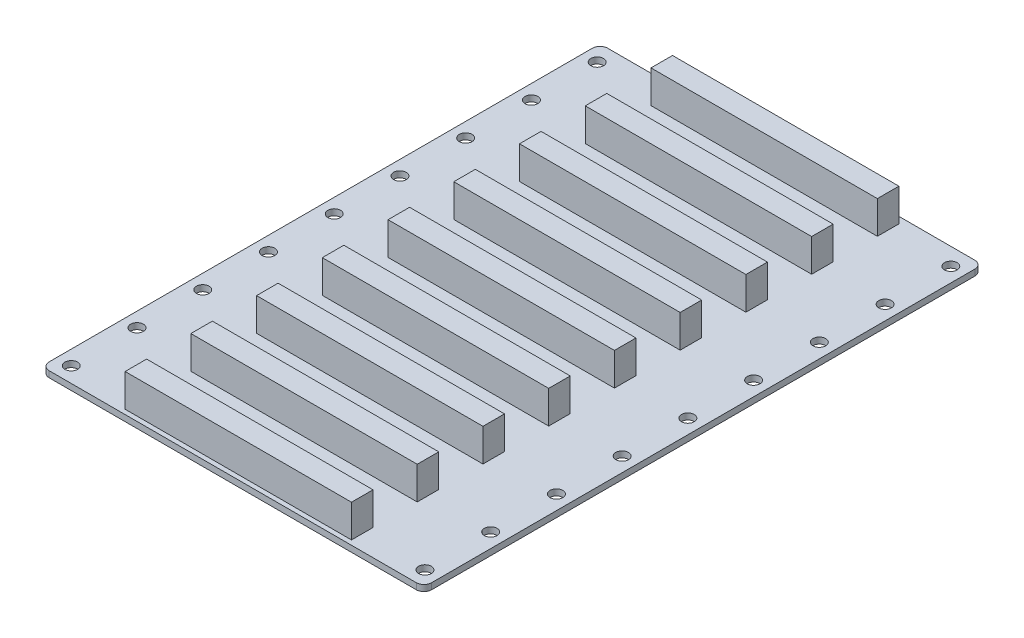
SolidWorks part; units mm, degrees
ref_plane "Front Plane" through (0, 0, 0) normal (0, 0, 1) x (1, 0, 0)
ref_plane "Top Plane" through (0, 0, 0) normal (0, 1, 0) x (1, 0, 0)
ref_plane "Right Plane" through (0, 0, 0) normal (1, 0, 0) x (0, 0, -1)
sketch "Sketch1" plane through (0, 0, 0) normal (0, 1, 0) x (1, 0, 0)
  line L1 (-49.75, -72.65) -> (49.75, -72.65)
  line L2 (-49.75, -72.65) -> (-49.75, 72.65)
  line L3 (-49.75, 72.65) -> (49.75, 72.65)
  line L4 (49.75, -72.65) -> (49.75, 72.65)
  line L5 (-49.75, -72.65) -> (49.75, 72.65) construction
  line L6 (-49.75, 72.65) -> (49.75, -72.65) construction
  point P0 (0, 0)
  dimension "D1" = 99.5
  dimension "D2" = 145.3
extrude "Boss-Extrude1" add sketch "Sketch1" along normal blind 1.6
sketch "Sketch3" plane through (0, 1.6, 0) normal (0, 1, 0) x (1, 0, 0)
  line L0 (0, 72.65) -> (0, -72.65) construction
  line L1 (49.75, 72.65) -> (-49.75, 72.65) construction
  line L2 (-49.75, -72.65) -> (49.75, -72.65) construction
  line L4 (-49.75, 72.65) -> (-49.75, -72.65) construction
  circle A1 centre (-46, -68.65) radius 1.65
  circle A3 centre (-46, -51.55) radius 1.65
  circle A4 centre (-46, -34.45) radius 1.65
  circle A5 centre (-46, -17.35) radius 1.65
  circle A6 centre (-46, -0.25) radius 1.65
  circle A7 centre (-46, 16.85) radius 1.65
  circle A8 centre (-46, 33.95) radius 1.65
  circle A9 centre (-46, 51.05) radius 1.65
  circle A10 centre (-46, 68.15) radius 1.65
  circle A11 centre (46, 68.15) radius 1.65
  circle A12 centre (46, 51.05) radius 1.65
  circle A13 centre (46, 33.95) radius 1.65
  circle A14 centre (46, 16.85) radius 1.65
  circle A15 centre (46, -0.25) radius 1.65
  circle A16 centre (46, -17.35) radius 1.65
  circle A17 centre (46, -34.45) radius 1.65
  circle A18 centre (46, -51.55) radius 1.65
  circle A19 centre (46, -68.65) radius 1.65
  dimension "D1" = 3.3
  dimension "D2" = 3.75
  dimension "D3" = 9
  dimension "D4" = 17.1
  dimension "D5" = 4
extrude "Cut-Extrude2" cut sketch "Sketch3" against normal up to surface (1.6 mm away) up to face at (0, 0, 0)
sketch "Sketch4" plane through (0, 1.6, 0) normal (0, 1, 0) x (1, 0, 0)
  line L0 (-29.195, -54.35) -> (-29.195, -48.75)
  line L1 (-29.195, -71.45) -> (29.695, -71.45)
  line L2 (-29.195, -71.45) -> (-29.195, -65.85)
  line L3 (-29.195, -65.85) -> (29.695, -65.85)
  line L4 (29.695, -71.45) -> (29.695, -65.85)
  line L5 (-29.195, -71.45) -> (29.695, -65.85) construction
  line L6 (-29.195, -65.85) -> (29.695, -71.45) construction
  line L7 (-49.75, -72.65) -> (49.75, -72.65) construction
  line L8 (49.75, -72.65) -> (49.75, 72.65) construction
  line L9 (-29.195, -54.35) -> (29.695, -54.35)
  line L10 (29.695, -54.35) -> (29.695, -48.75)
  line L11 (-29.195, -48.75) -> (29.695, -48.75)
  line L12 (-29.195, -37.25) -> (-29.195, -31.65)
  line L13 (-29.195, -37.25) -> (29.695, -37.25)
  line L14 (29.695, -37.25) -> (29.695, -31.65)
  line L15 (-29.195, -31.65) -> (29.695, -31.65)
  line L16 (-29.195, -20.15) -> (-29.195, -14.55)
  line L17 (-29.195, -20.15) -> (29.695, -20.15)
  line L18 (29.695, -20.15) -> (29.695, -14.55)
  line L19 (-29.195, -14.55) -> (29.695, -14.55)
  line L20 (-29.195, -3.05) -> (-29.195, 2.55)
  line L21 (-29.195, -3.05) -> (29.695, -3.05)
  line L22 (29.695, -3.05) -> (29.695, 2.55)
  line L23 (-29.195, 2.55) -> (29.695, 2.55)
  line L24 (-29.195, 14.05) -> (-29.195, 19.65)
  line L25 (-29.195, 14.05) -> (29.695, 14.05)
  line L26 (29.695, 14.05) -> (29.695, 19.65)
  line L27 (-29.195, 19.65) -> (29.695, 19.65)
  line L28 (-29.195, 31.15) -> (-29.195, 36.75)
  line L29 (-29.195, 31.15) -> (29.695, 31.15)
  line L30 (29.695, 31.15) -> (29.695, 36.75)
  line L31 (-29.195, 36.75) -> (29.695, 36.75)
  line L32 (-29.195, 48.25) -> (-29.195, 53.85)
  line L33 (-29.195, 48.25) -> (29.695, 48.25)
  line L34 (29.695, 48.25) -> (29.695, 53.85)
  line L35 (-29.195, 53.85) -> (29.695, 53.85)
  line L36 (-29.195, 65.35) -> (-29.195, 70.95)
  line L37 (-29.195, 65.35) -> (29.695, 65.35)
  line L38 (29.695, 65.35) -> (29.695, 70.95)
  line L39 (-29.195, 70.95) -> (29.695, 70.95)
  point P0 (0.25, -68.65)
  dimension "D1" = 5.6
  dimension "D2" = 58.89
  dimension "D3" = 4
  dimension "D4" = 49.5
  dimension "D6" = 11.5
  dimension "D5" = 9
extrude "Boss-Extrude2" add sketch "Sketch4" along normal blind 8.5
fillet "Fillet2" radius 2 4 edges at (-49.75, 0.8, -72.65) (49.75, 0.8, -72.65) (49.75, 0.8, 72.65) (-49.75, 0.8, 72.65)
